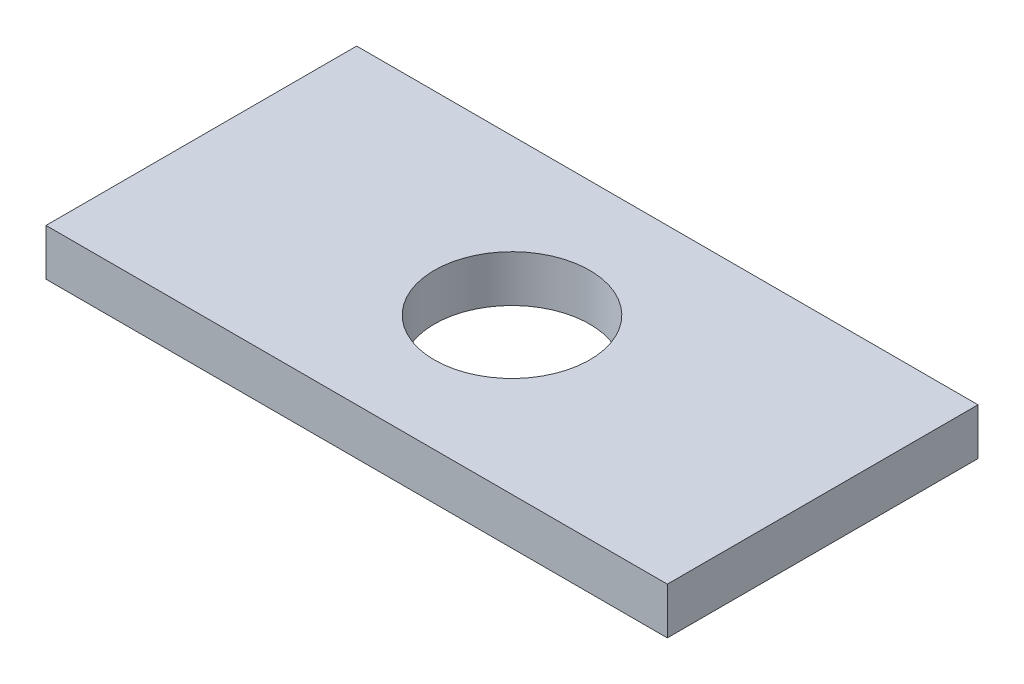
SolidWorks part; units mm, degrees
ref_plane "Alzado" through (0, 0, 0) normal (0, 0, 1) x (1, 0, 0)
ref_plane "Planta" through (0, 0, 0) normal (0, 1, 0) x (1, 0, 0)
ref_plane "Vista lateral" through (0, 0, 0) normal (1, 0, 0) x (0, 0, -1)
sketch "Croquis1" plane through (0, 0, 0) normal (0, 1, 0) x (1, 0, 0)
  line L1 (-20, -10) -> (20, -10)
  line L2 (-20, -10) -> (-20, 10)
  line L3 (-20, 10) -> (20, 10)
  line L4 (20, -10) -> (20, 10)
  line L5 (-20, -10) -> (20, 10) construction
  line L6 (-20, 10) -> (20, -10) construction
  point P0 (0, 0)
  dimension "D1" = 20
  dimension "D2" = 40
sheet metal parameters "Chapa metálica1" thickness 3 parameters "D1"=0.7366, "Espesor"=3
base flange "Brida base1" sketch "Croquis1" thickness 3 reverse thickness direction no parameters "D1"=0.7366
sketch "Croquis5" plane through (0, 0, 0) normal (0, 1, 0) x (1, 0, 0)
  circle A0 centre (0, 0) radius 5
  dimension "D1" = 10
extrude "Cortar-Extruir1" cut sketch "Croquis5" against normal through all normal cut yes
flat pattern "Chapa desplegada1" [suppressed]
sketch "Líneas de pliegue1" plane through (0, 0, 0) normal (0, 1, 0) x (-1, 0, 0)
sketch3d "Cuadro delimitador1" [suppressed]
  line L0 (0, 0, 0) -> (-40, 0, 0) construction
  line L1 (0, 20, 0) -> (-40, 20, 0) construction
  line L2 (0, 0, 0) -> (0, 20, 0) construction
  line L3 (-40, 0, 0) -> (-40, 20, 0) construction
